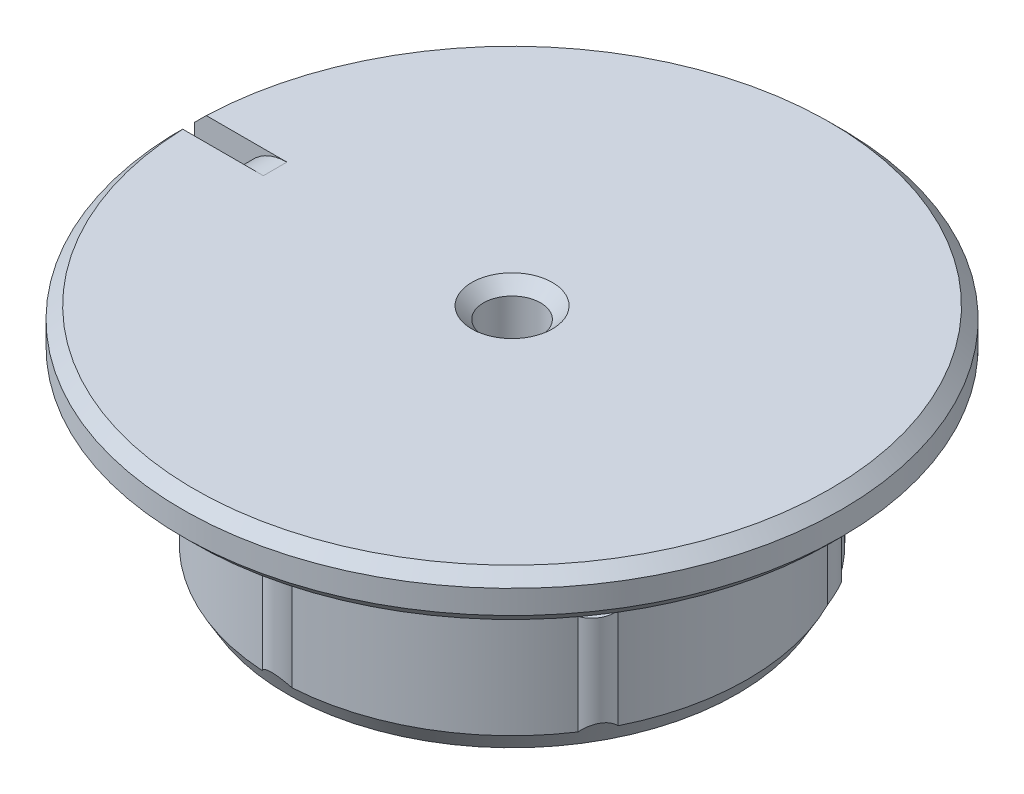
SolidWorks part; units mm, degrees
ref_plane "Front Plane" through (0, 0, 0) normal (0, 0, 1) x (1, 0, 0)
ref_plane "Top Plane" through (0, 0, 0) normal (0, 1, 0) x (1, 0, 0)
ref_plane "Right Plane" through (0, 0, 0) normal (1, 0, 0) x (0, 0, -1)
sketch "Sketch1" plane through (0, 0, 0) normal (0, 0, 1) x (1, 0, 0)
  line L0 (0, 0) -> (0, 30415.8317) construction
  line L1 (0, 0) -> (20, 0)
  line L2 (20, 0) -> (20, 15)
  line L3 (20, 15) -> (28, 15)
  line L4 (28, 15) -> (28, 19)
  line L5 (28, 19) -> (2.425, 19)
  line L6 (2.425, 19) -> (2.425, 9)
  line L7 (2.425, 9) -> (0, 9)
  line L9 (0, 9) -> (0, 0)
  dimension "D1" = 40
  dimension "D2" = 4.85
  dimension "D3" = 15
  dimension "D4" = 4
  dimension "D5" = 10
  dimension "D6" = 8
revolve "Revolve1" add sketch "Sketch1" angle 360 about L0
sketch "Sketch2" plane through (0, 0, 0) normal (0, -1, 0) x (1, 0, 0)
  arc A0 (-1.25, 19.9609) -> (1.25, 19.9609) centre (0, 18.4888) cw
  circle A1 centre (0, 0) radius 20 construction
  circle A2 centre (0, 0) radius 20 construction
  arc A3 (-1.25, 19.9609) -> (-16.6616, 11.063) centre (0, 0) ccw
  arc A4 (16.6616, 11.063) -> (17.9116, 8.8979) centre (16.0117, 9.2444) cw
  arc A5 (17.9116, -8.8979) -> (16.6616, -11.063) centre (16.0117, -9.2444) cw
  arc A6 (1.25, -19.9609) -> (-1.25, -19.9609) centre (0, -18.4888) cw
  arc A7 (-16.6616, -11.063) -> (-17.9116, -8.8979) centre (-16.0117, -9.2444) cw
  arc A8 (-17.9116, 8.8979) -> (-16.6616, 11.063) centre (-16.0117, 9.2444) cw
  arc A9 (-17.9116, 8.8979) -> (-17.9116, -8.8979) centre (0, 0) ccw
  arc A10 (-16.6616, -11.063) -> (-1.25, -19.9609) centre (0, 0) ccw
  arc A11 (1.25, -19.9609) -> (16.6616, -11.063) centre (0, 0) ccw
  arc A12 (17.9116, -8.8979) -> (17.9116, 8.8979) centre (0, 0) ccw
  arc A13 (16.6616, 11.063) -> (1.25, 19.9609) centre (0, 0) ccw
  point P27 (0, 0)
  dimension "D2" = 20.42
  dimension "D1" = 2.5
  dimension "D3" = 6
extrude "Boss-Extrude1" add sketch "Sketch2" against normal offset from surface (10 mm away) 5 up to face at (0, 15, -28)
sketch "Sketch3" plane through (0, 0, 0) normal (0, 0, 1) x (1, 0, 0)
  line L0 (-21, 3.2321) -> (-18.5566, -1)
  line L1 (-18.5566, -1) -> (-21, -1)
  line L2 (-21, -1) -> (-21, 3.2321)
  line L3 (-20, 0) -> (-17.9116, 0) construction
  dimension "D1" = 0.75
  dimension "D2" = 1
  dimension "D3" = 1
  dimension "D4" = 60
ref_axis "Axis1" through (0, 29.3369, 0) along (0, -1, 0)
revolve "Cut-Revolve1" cut sketch "Sketch3" angle 360 about axis through (0, 29.3369, 0) along (0, -1, 0)
chamfer "Chamfer1" distance 1 angle 45 3 edges at (0, 19, -2.425) (0, 15, -28) (0, 19, -28)
sketch "Sketch4" plane through (0, 0, 0) normal (0, -1, 0) x (1, 0, 0)
  line L0 (-24.13, 1) -> (-28, 1)
  line L1 (-28, -1) -> (-24.13, -1)
  line L2 (-28, 1) -> (-28, -1)
  line L3 (-24.13, -1) -> (-24.13, 1)
  point P2 (-21.9592, -1)
  point P5 (-28, 0)
  point P8 (-19.975, -1)
  dimension "D1" = 2
  dimension "D2" = 28
  dimension "D3" = 24.13
extrude "Cut-Extrude1" cut sketch "Sketch4" against normal through all
fillet "Fillet1" radius 4 1 edges at (-24.13, 19, 0)
